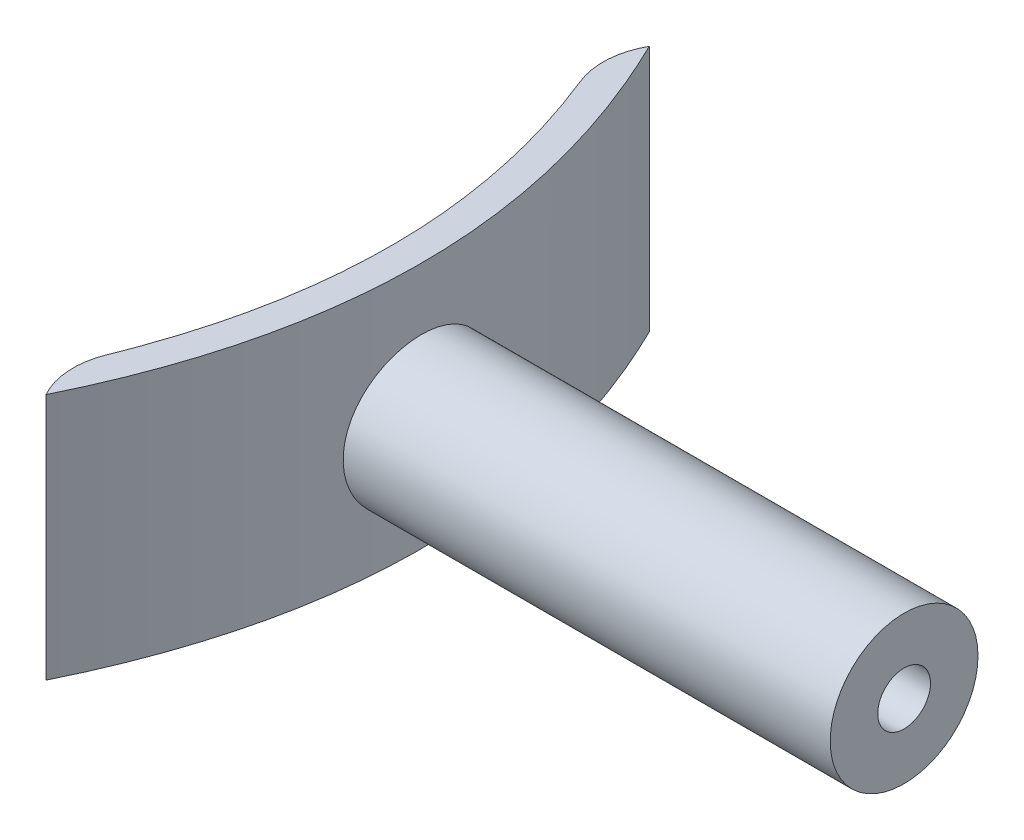
SolidWorks part; units mm, degrees
ref_plane "Front Plane" through (0, 0, 0) normal (0, 0, 1) x (1, 0, 0)
ref_plane "Top Plane" through (0, 0, 0) normal (0, 1, 0) x (1, 0, 0)
ref_plane "Right Plane" through (0, 0, 0) normal (1, 0, 0) x (0, 0, -1)
sketch "Sketch1" plane through (0, 0, 0) normal (0, 1, 0) x (1, 0, 0)
  line L3 (8.3059, -19.1203) -> (10.102, -20)
  line L4 (8.3058, 19.1205) -> (10.1019, 20.0003)
  spline S0 degree 3 poles (10.1019, 20.0003) (13.3673, 13.3335) (16.6327, 0.0001) (13.3673, -13.3333) (10.102, -20) knots 0.214282 0.214282 0.214282 0.214282 0.5 0.785714 0.785714 0.785714 0.785714
  spline S1 degree 1 poles (8.3058, 19.1205) (8.3059, -19.1203) knots 0 0 1 1 construction
  spline S2 degree 3 poles (8.3058, 19.1205) (8.6943, 18.3273) (9.4389, 16.7066) (10.7095, 13.5117) (11.9315, 9.5203) (12.8059, 4.7555) (13.0971, 0.0001) (12.8059, -4.7553) (11.9316, -9.52) (10.7096, -13.5115) (9.439, -16.7063) (8.6944, -18.327) (8.3059, -19.1203) knots 0.214282 0.214282 0.214282 0.214282 0.249996 0.285711 0.35714 0.428569 0.499998 0.571427 0.642856 0.714285 0.75 0.785714 0.785714 0.785714 0.785714
extrude "Boss-Extrude1" add sketch "Sketch1" along normal blind 18
ref_plane "Plane1" through (18, 0, 0) normal (1, 0, 0) x (0, 0, -1)
sketch "Sketch2" plane through (18, 0, 0) normal (1, 0, 0) x (0, 0, -1)
  line L0 (0.0001, 0) -> (0.0001, 18) construction
  line L1 (-20, 0) -> (20.0003, 0) construction
  line L2 (20.0003, 18) -> (-20, 18) construction
  circle A0 centre (0, 9) radius 4.9
extrude "Boss-Extrude2" add sketch "Sketch2" against normal up to surface (3.294 mm away) up to face at (10.102, 9, 9.9999)
sketch "Sketch3" plane through (18, 0, 0) normal (1, 0, 0) x (0, 0, -1)
  circle A1 centre (0, 9) radius 4.9
  circle A2 centre (0, 9) radius 4.9
  dimension "D1" = 0
extrude "Boss-Extrude3" add sketch "Sketch3" along normal blind 29
sketch "Sketch4" plane through (47, 0, 0) normal (1, 0, 0) x (0, 0, -1)
  circle A0 centre (0, 9) radius 1.75
extrude "Cut-Extrude1" cut sketch "Sketch4" against normal blind 29
sketch "Sketch5" plane through (47, 0, 0) normal (1, 0, 0) x (0, 0, -1)
  line L0 (-20, 1.6) -> (20.0003, 1.6)
  line L1 (-20, 18) -> (-20, 0) construction
  line L2 (20.0003, 18) -> (20.0003, 0) construction
  line L4 (-20, 1.6) -> (-20, 0)
  line L5 (-20, 0) -> (20.0003, 0)
  line L6 (20.0003, 0) -> (20.0003, 1.6)
extrude "Cut-Extrude2" cut sketch "Sketch5" against normal blind 40
fillet "Fillet1" radius 5 2 edges at (8.3058, 9.8, -19.1205) (8.3059, 9.8, 19.1203)
